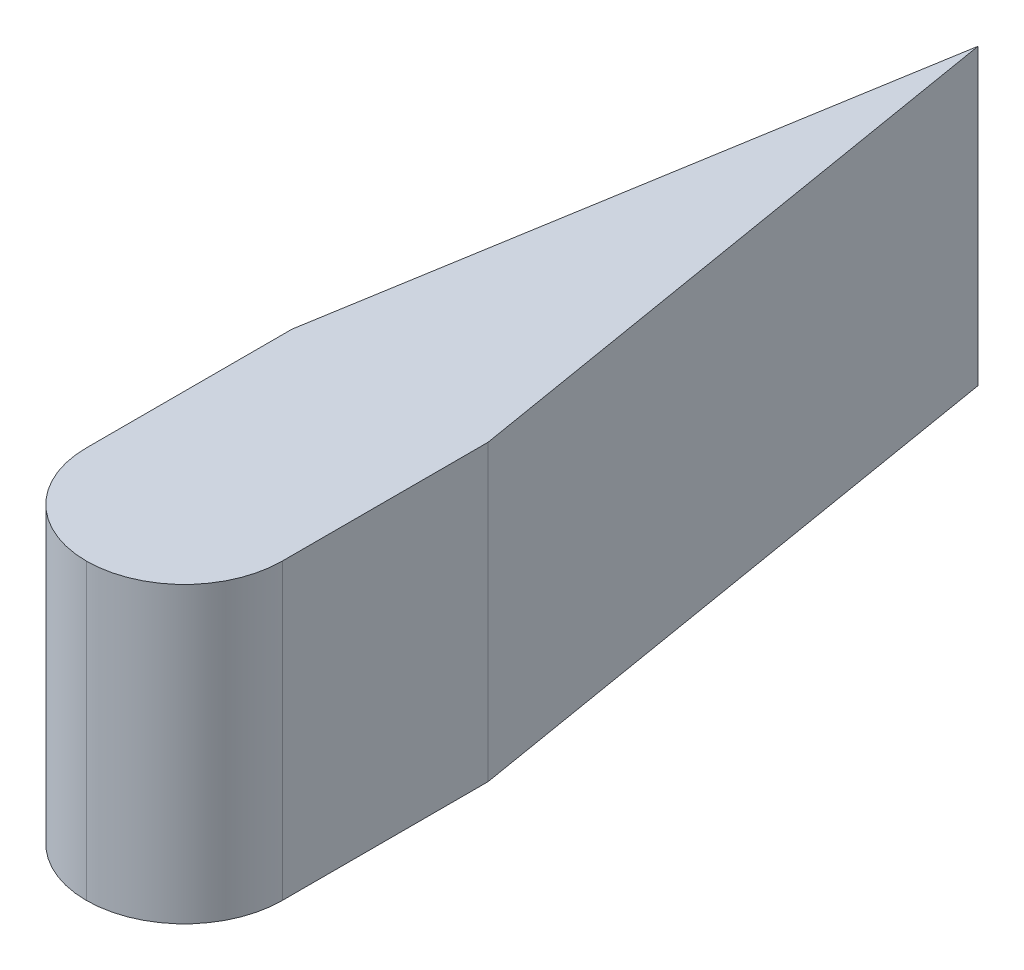
SolidWorks part; units mm, degrees
material "1023 Carbon Steel Sheet (SS)"
ref_plane "Front Plane" through (0, 0, 0) normal (0, 0, 1) x (1, 0, 0)
ref_plane "Top Plane" through (0, 0, 0) normal (0, 1, 0) x (1, 0, 0)
ref_plane "Right Plane" through (0, 0, 0) normal (1, 0, 0) x (0, 0, -1)
sketch "Sketch1" plane through (0, 0, 0) normal (0, 1, 0) x (1, 0, 0)
  line L0 (0, 0) -> (0, 38.1) construction
  line L1 (0, 38.1) -> (-6.35, 0)
  line L2 (0, 38.1) -> (6.35, 0)
  line L3 (-6.35, 0) -> (-6.35, -19.685)
  line L4 (-6.35, -19.685) -> (6.35, -19.685)
  line L5 (6.35, 0) -> (6.35, -19.685)
  dimension "D1" = 38.1
  dimension "D2" = 6.35
  dimension "D3" = 6.35
  dimension "D4" = 19.685
  dimension "D5" = 12.7
extrude "Boss-Extrude1" add sketch "Sketch1" along normal blind 19.05
fillet "Fillet1" radius 6.35 2 edges at (-6.35, 9.525, 19.685) (6.35, 9.525, 19.685)
sketch "Sketch2" plane through (0, 19.05, 0) normal (0, 1, 0) x (1, 0, 0)
  arc A0 (1.1714, -14.0578) -> (-1.1714, -13.1855) centre (0, -13.6217) ccw construction
  arc A1 (1.1714, -14.0578) -> (-1.1714, -13.1855) centre (0, -13.6217) ccw
sketch "Sketch3" plane through (0, 0, 0) normal (0, -1, 0) x (1, 0, 0)
  arc A0 (-1.1714, 13.1855) -> (1.1714, 14.0578) centre (0, 13.6217) ccw construction
  arc A1 (-1.1714, 13.1855) -> (1.1714, 14.0578) centre (0, 13.6217) ccw
  circle A2 centre (0, 13.6217) radius 3.3536
extrude "Cut-Extrude1" cut sketch "Sketch3" against normal blind 12.7 contours A2 region at (0, 0, 13.6217)
